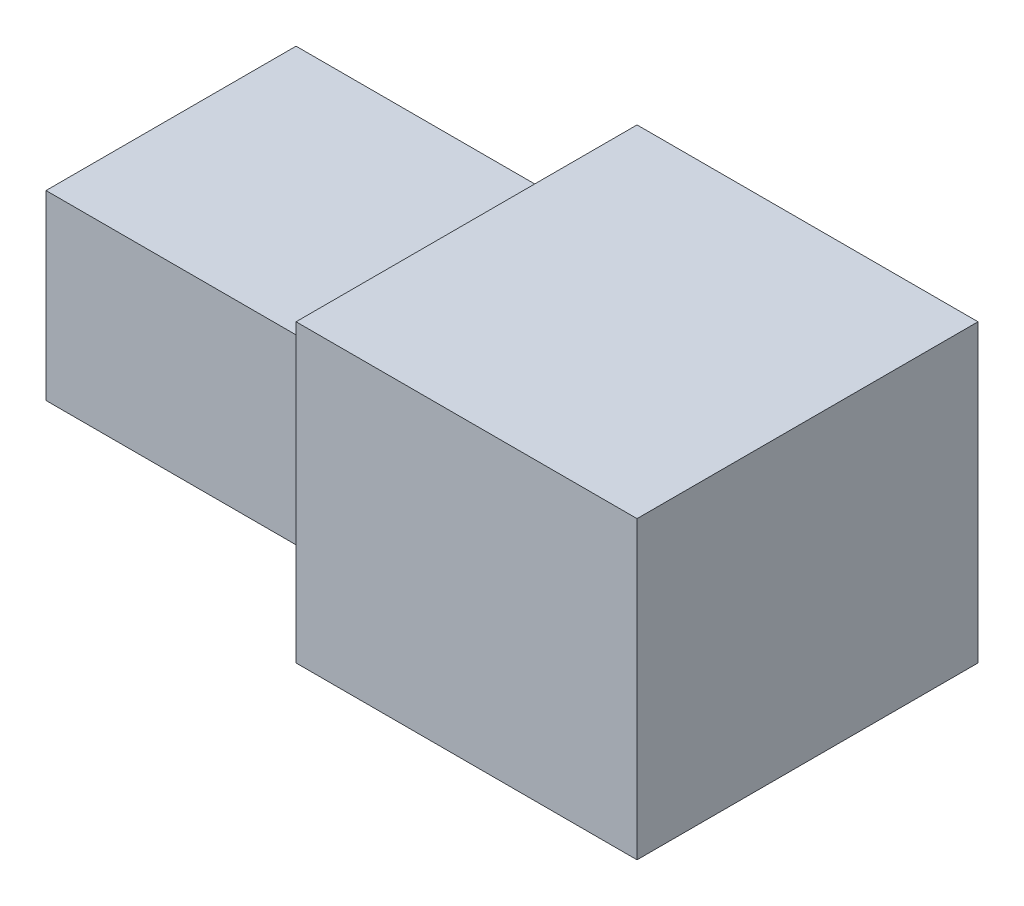
SolidWorks part; units mm, degrees
ref_plane "Front Plane" through (0, 0, 0) normal (0, 0, 1) x (1, 0, 0)
ref_plane "Top Plane" through (0, 0, 0) normal (0, 1, 0) x (1, 0, 0)
ref_plane "Right Plane" through (0, 0, 0) normal (1, 0, 0) x (0, 0, -1)
sketch "Sketch1" plane through (0, 0, 0) normal (0, 0, 1) x (1, 0, 0)
  line L1 (-9.525, 8.255) -> (9.525, 8.255)
  line L2 (-9.525, 8.255) -> (-9.525, -8.255)
  line L3 (-9.525, -8.255) -> (9.525, -8.255)
  line L4 (9.525, 8.255) -> (9.525, -8.255)
  line L5 (-9.525, 8.255) -> (9.525, -8.255) construction
  line L6 (-9.525, -8.255) -> (9.525, 8.255) construction
  line L10 (-9.525, 5.08) -> (-9.525, -5.08)
  point P0 (0, 0)
  point P6 (-25.4, 0)
  dimension "D1" = 19.05
  dimension "D2" = 16.51
extrude "Boss-Extrude1" add sketch "Sketch1" along normal blind 19.05 contours L4 L1 L2 L3 region at (0, 0, 0)
sketch "Sketch2" plane through (0, 0, 0) normal (0, 0, 1) x (1, 0, 0)
  line L1 (-26.035, 5.08) -> (-9.525, 5.08)
  line L2 (-26.035, 5.08) -> (-26.035, -5.08)
  line L3 (-26.035, -5.08) -> (-9.525, -5.08)
  line L4 (-9.525, 5.08) -> (-9.525, -5.08)
  line L5 (-26.035, 5.08) -> (-9.525, -5.08) construction
  line L6 (-26.035, -5.08) -> (-9.525, 5.08) construction
  point P0 (-25.4, 0)
  dimension "D1" = 16.51
extrude "Boss-Extrude2" add sketch "Sketch2" along normal blind 16.51 contours L2 L1 L4 L3
sketch "Sketch3" plane through (0, 0, 0) normal (0, 0, -1) x (-1, 0, 0)
  line L6 (26.035, 5.08) -> (9.525, 5.08)
  line L13 (26.035, 5.08) -> (26.035, -5.08)
  line L14 (26.035, -5.08) -> (9.525, -5.08)
  line L15 (9.525, 5.08) -> (9.525, -5.08)
  point P0 (25.4, 0)
extrude "Cut-Extrude1" cut sketch "Sketch3" against normal blind 2.54
shell "Shell1" thickness 1.27 removed face at (-26.035, 0, 9.525)
sketch "Sketch4" plane through (8.255, 0, 0) normal (-1, 0, 0) x (0, 0, 1)
  line L1 (8.255, 1.27) -> (10.795, 1.27)
  line L2 (8.255, 1.27) -> (8.255, -1.27)
  line L3 (8.255, -1.27) -> (10.795, -1.27)
  line L4 (10.795, 1.27) -> (10.795, -1.27)
  line L5 (8.255, 1.27) -> (10.795, -1.27) construction
  line L6 (8.255, -1.27) -> (10.795, 1.27) construction
  line L7 (3.81, 0.635) -> (8.255, 0.635)
  line L8 (3.81, 0.635) -> (3.81, -0.635)
  line L9 (3.81, -0.635) -> (8.255, -0.635)
  line L10 (8.255, 0.635) -> (8.255, -0.635)
  line L11 (3.81, 0.635) -> (8.255, -0.635) construction
  line L12 (3.81, -0.635) -> (8.255, 0.635) construction
  line L13 (8.89, -3.81) -> (10.16, -3.81)
  line L14 (8.89, -3.81) -> (8.89, -1.27)
  line L15 (8.89, -1.27) -> (10.16, -1.27)
  line L16 (10.16, -3.81) -> (10.16, -1.27)
  line L17 (8.89, -3.81) -> (10.16, -1.27) construction
  line L18 (8.89, -1.27) -> (10.16, -3.81) construction
  line L19 (15.24, -0.635) -> (10.795, -0.635)
  line L20 (15.24, -0.635) -> (15.24, 0.635)
  line L21 (15.24, 0.635) -> (10.795, 0.635)
  line L22 (10.795, -0.635) -> (10.795, 0.635)
  line L23 (15.24, -0.635) -> (10.795, 0.635) construction
  line L24 (15.24, 0.635) -> (10.795, -0.635) construction
  line L25 (8.89, 3.81) -> (10.16, 3.81)
  line L26 (8.89, 3.81) -> (8.89, 1.27)
  line L27 (8.89, 1.27) -> (10.16, 1.27)
  line L28 (10.16, 3.81) -> (10.16, 1.27)
  line L29 (8.89, 3.81) -> (10.16, 1.27) construction
  line L30 (8.89, 1.27) -> (10.16, 3.81) construction
  line L31 (19.05, 8.255) -> (0, 8.255) construction
  line L32 (9.525, 8.255) -> (9.525, -8.255) construction
  line L33 (19.05, -8.255) -> (0, -8.255) construction
  line L34 (15.24, -3.81) -> (3.81, -3.81) construction
  line L35 (3.81, -3.81) -> (3.81, 3.81) construction
  line L36 (15.24, 3.81) -> (3.81, 3.81) construction
  line L37 (15.24, 3.81) -> (15.24, -3.81) construction
  point P0 (9.525, 0)
  point P5 (6.0325, 0)
  point P10 (9.525, -2.54)
  point P15 (13.0175, 0)
  point P20 (9.525, 2.54)
  point P37 (8.255, 0)
  dimension "D1" = 2.54
  dimension "D2" = 2.54
  dimension "D3" = 1.27
  dimension "D4" = 1.27
  dimension "D5" = 1.27
  dimension "D6" = 1.27
extrude "Boss-Extrude3" add sketch "Sketch4" along normal blind 33.02 contours L4 L1 L2 L3 | L20 L21 L4 L19 | L28 L25 L26 L1 | L8 L9 L2 L7 | L13 L16 L3 L14 region at (8.255, 0, 9.525) region at (8.255, 2.54, 9.525) region at (8.255, 0, 6.0325) region at (8.255, 0, 13.0175) region at (8.255, -2.54, 9.525)
fillet "Fillet1" radius 0.508 8 edges at (-24.765, 1.27, 8.5725) (-24.765, 0.9525, 8.255) (-24.765, -1.27, 8.5725) (-24.765, -0.9525, 8.255) (-24.765, -0.9525, 10.795) (-24.765, -1.27, 10.4775) (-24.765, 1.27, 10.4775) (-24.765, 0.9525, 10.795)
fillet "Fillet2" radius 1.27 4 edges at (-24.765, 0, 15.24) (-24.765, 0, 3.81) (-24.765, 3.81, 9.525) (-24.765, -3.81, 9.525)
fillet "Fillet3" radius 0.635 16 edges at (-25.137, -0.635, 4.182) (-25.137, -3.438, 8.89) (-25.137, -3.438, 10.16) (-25.137, 3.438, 8.89) (-25.137, 3.438, 10.16) (-25.137, 0.635, 14.868) (-25.137, 0.635, 4.182) (-24.765, -0.635, 6.9215) (-24.765, -1.651, 8.89) (-24.765, -1.651, 10.16) (-24.765, 1.651, 8.89) (-24.765, 1.651, 10.16) (-24.765, 0.635, 12.1285) (-24.765, 0.635, 6.9215) (-25.137, -0.635, 14.868) (-24.765, -0.635, 12.1285)
equation "\"v05\"=0.276019"
